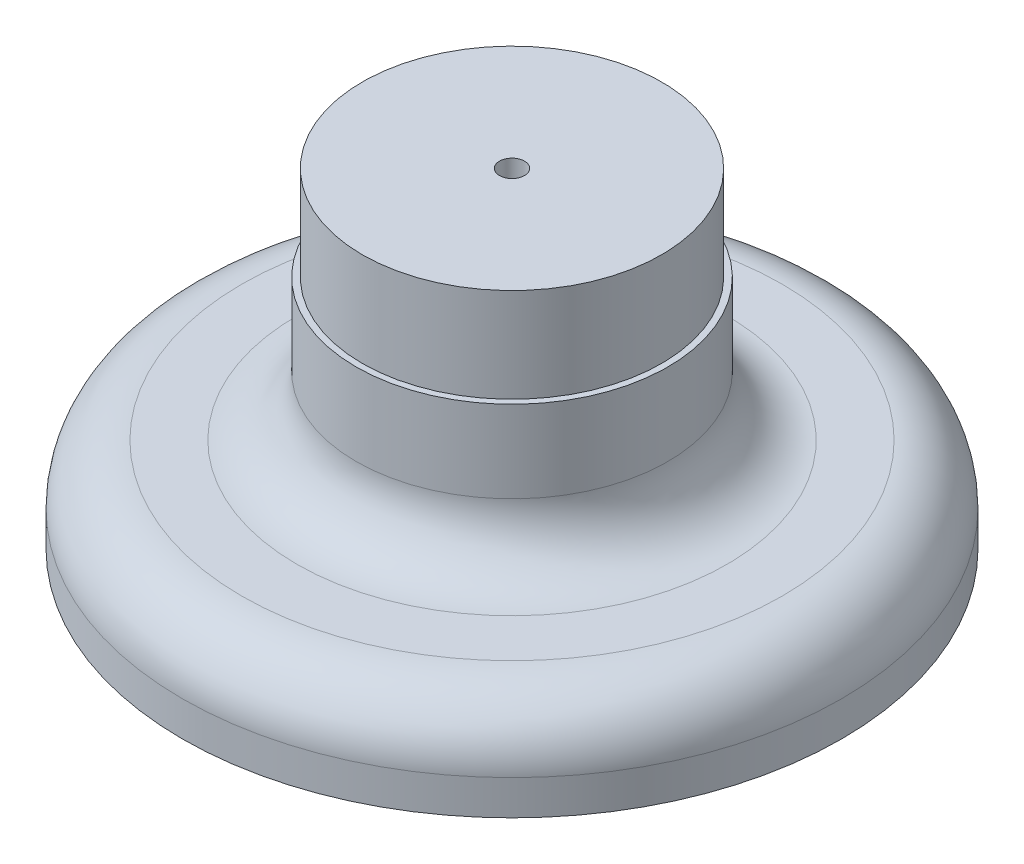
SolidWorks part; units mm, degrees
ref_plane "Front Plane" through (0, 0, 0) normal (0, 0, 1) x (1, 0, 0)
ref_plane "Top Plane" through (0, 0, 0) normal (0, 1, 0) x (1, 0, 0)
ref_plane "Right Plane" through (0, 0, 0) normal (1, 0, 0) x (0, 0, -1)
sketch "Sketch1" plane through (0, 0, 0) normal (0, 1, 0) x (1, 0, 0)
  circle A0 centre (0, 0) radius 40.386
  circle A1 centre (0, 0) radius 42.037
  circle A2 centre (0, 0) radius 88.9
extrude "Boss-Extrude1" add sketch "Sketch1" along normal blind 88.9 contours A0 region at (0, 0, 0)
extrude "Boss-Extrude2" add sketch "Sketch1<3>" along normal blind 63.5 contours A1 A0 region at (-40.848, 0, 0)
sketch "Sketch1<3>" plane through (0, 0, 0) normal (0, 1, 0) x (1, 0, 0) same geometry as "Sketch1"
extrude "Boss-Extrude3" add sketch "Sketch1<4>" along normal blind 25.4 contours A2 A1 region at (-86.3855, 0, 0)
sketch "Sketch1<4>" plane through (0, 0, 0) normal (0, 1, 0) x (1, 0, 0) same geometry as "Sketch1"
hole_wizard "CSK for 1/4 Flat Head Machine Screw (100)1" positions "Sketch2" profile "Sketch3" countersink size "1/4" standard "ANSI Inch" end condition through all
sketch "Sketch2" plane through (0, 0, 0) normal (0, -1, 0) x (-1, 0, 0)
  point P0 (0, 0)
sketch "Sketch3" plane through (0, 0, 0) normal (1, 0, 0) x (0, 0, -1)
  line L0 (0, 0) -> (0, 88.9)
  line L1 (0, 88.9) -> (3.3782, 88.9)
  line L2 (3.3782, 88.9) -> (3.3782, 2.5682)
  line L3 (3.3782, 2.5682) -> (6.4389, 0)
  line L5 (6.4389, 0) -> (0, 0)
  line L6 (-3.3782, 2.5682) -> (-6.4389, 0) construction
  line L11 (0, -6.35) -> (0, 107.95) construction
  dimension "Thru Hole Dia." = 6.7564
  dimension "Thru Hole Depth" = 88.9
  dimension "Near C'Sink Dia." = 12.8778
  dimension "Near C'Sink Angle" = 100
fillet "Fillet1" radius 16.002 1 edges at (0, 25.4, 42.037)
fillet "Fillet2" radius 16.002 1 edges at (0, 25.4, 88.9)
